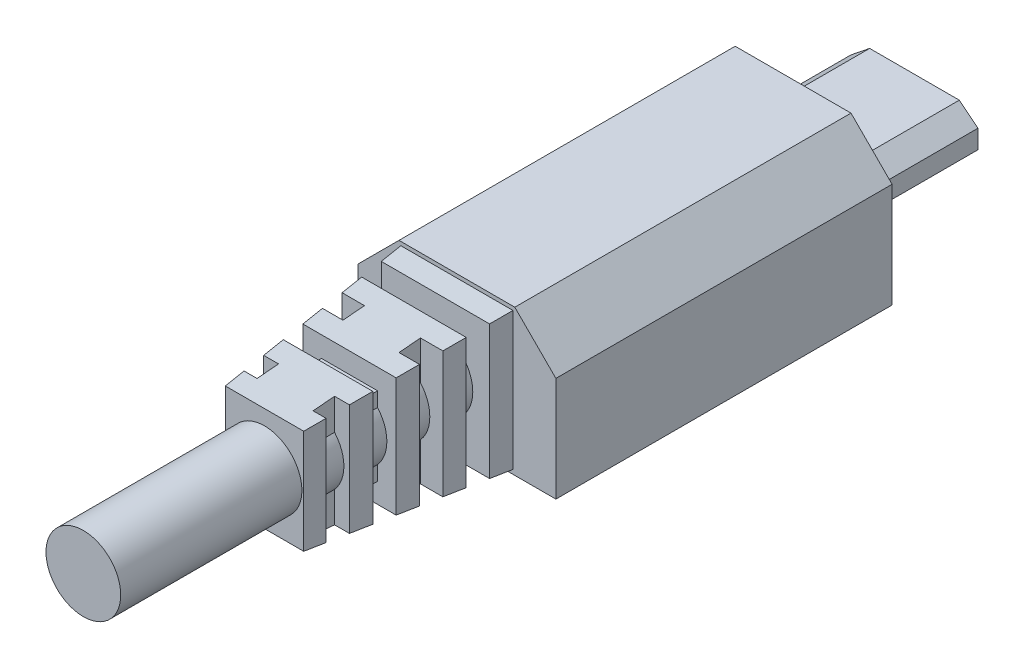
SolidWorks part; units mm, degrees
ref_plane "Front Plane" through (0, 0, 0) normal (0, 0, 1) x (1, 0, 0)
ref_plane "Top Plane" through (0, 0, 0) normal (0, 1, 0) x (1, 0, 0)
ref_plane "Right Plane" through (0, 0, 0) normal (1, 0, 0) x (0, 0, -1)
sketch "Sketch1" plane through (0, 0, 0) normal (0, 0, 1) x (1, 0, 0)
  line L0 (0, 1) -> (1, 1.8)
  line L1 (0, 0) -> (6.8, 0)
  line L2 (0, 0) -> (0, 1.8)
  line L3 (0, 1.8) -> (6.8, 1.8)
  line L4 (6.8, 0) -> (6.8, 1.8)
  line L5 (3.4, 1.8) -> (3.4, 0) construction
  line L6 (6.8, 1) -> (5.8, 1.8)
  line L8 (1.55, 0.2) -> (5.25, 0.2)
  line L9 (1.55, 0.2) -> (1.55, 0.85)
  line L10 (1.55, 0.85) -> (5.25, 0.85)
  line L11 (5.25, 0.2) -> (5.25, 0.85)
  point P15 (3.4, 0.85)
  dimension "D1" = 1.8
  dimension "D2" = 6.8
  dimension "D3" = 1
  dimension "D4" = 1
  dimension "D5" = 0.2
  dimension "D6" = 3.7
  dimension "D7" = 0.65
extrude "Boss-Extrude1" add sketch "Sketch1" along normal blind 6.5 contours L5 L3 L0 L2 L1 L8 L9 L10 | L3 L5 L10 L11 L8 L1 L4 L6 region at (1.6147, 0.9437, 0) region at (5.1853, 0.9437, 0)
sketch "Sketch2" plane through (0, 0, 6.5) normal (0, 0, 1) x (1, 0, 0)
  line L0 (0, 0.7631) -> (-1.9, 0.7631) construction
  line L1 (-1.9, 4.8) -> (8.7, 4.8)
  line L2 (-1.9, 4.8) -> (-1.9, -3)
  line L3 (-1.9, -3) -> (8.7, -3)
  line L4 (8.7, 4.8) -> (8.7, -3)
  line L5 (-1.9, 2.6) -> (0.3, 4.8)
  line L6 (8.7, 2.6) -> (6.5, 4.8)
  line L7 (3.4, 4.8) -> (3.4, 1.8) construction
  line L8 (1, 1.8) -> (5.8, 1.8) construction
  line L9 (3.4, 0) -> (3.4, -3) construction
  line L10 (0, 0) -> (6.8, 0) construction
  line L13 (0, 0) -> (0, 1) construction
  line L14 (6.8, 0.7631) -> (8.7, 0.7631) construction
  line L15 (6.8, 0) -> (6.8, 1) construction
  line M1 (1.55, 0.85) -> (5.25, 0.85)
  line M2 (5.25, 0.85) -> (5.25, 0.2)
  line M3 (5.25, 0.2) -> (1.55, 0.2)
  line M4 (1.55, 0.2) -> (1.55, 0.85)
  line M5 (6.8, 1) -> (5.8, 1.8)
  line M6 (5.8, 1.8) -> (1, 1.8)
  line M7 (1, 1.8) -> (0, 1)
  line M8 (0, 1) -> (0, 0)
  line M9 (0, 0) -> (6.8, 0)
  line M10 (6.8, 0) -> (6.8, 1)
  dimension "D1" = 10.6
  dimension "D2" = 7.8
  dimension "D3" = 2.2
  dimension "D4" = 2.2
extrude "Boss-Extrude2" add sketch "Sketch2" along normal blind 18 contours L4 L6 L1 L5 L2 L3 M5 M10 M9 M8 M7 M6 | M10 M5 M6 M7 M8 M9 M4 M1 M2 M3 | M1 M4 M3 M2 region at (3.4, 4.6684, 6.5) region at (3.4, 0.525, 6.5) region at (3.4, 0.9437, 6.5)
sketch "Sketch5" plane through (0, 0, 24.5) normal (0, 0, 1) x (1, 0, 0)
  line L0 (0.3, 4.8) -> (6.5, 4.8) construction
  line L1 (6.4, 4.6) -> (0.4, 4.6)
  line L2 (6.4, 4.6) -> (6.4, -2.772)
  line L3 (6.4, -2.772) -> (0.4, -2.772)
  line L4 (0.4, 4.6) -> (0.4, -2.772)
  line L6 (3.4, 4.8) -> (3.4, 4.6) construction
  dimension "D1" = 0.2
  dimension "D2" = 6
extrude "Boss-Extrude4" add sketch "Sketch5" along normal blind 10.3 draft 5
sketch "Sketch7" plane through (0, 4.8, 0) normal (0, 1, 0) x (1, 0, 0)
  line L0 (3.4, -24.5) -> (3.4, -36.1996) construction
  line L1 (0.3, -24.5) -> (1.9, -24.5)
  line L2 (0.3, -24.5) -> (0.3, -25.65)
  line L3 (0.3, -25.65) -> (1.9, -25.65)
  line L4 (1.9, -24.5) -> (1.9, -25.65)
  line L5 (1.9, -25.65) -> (-0.2696, -25.65)
  line L6 (1.9, -25.65) -> (1.9, -26.8)
  line L7 (1.9, -26.8) -> (-0.2696, -26.8)
  line L8 (-0.2696, -25.65) -> (-0.2696, -26.8)
  line L9 (1.9, -26.8) -> (-0.2696, -26.8)
  line L10 (1.9, -26.8) -> (1.9, -27.95)
  line L11 (1.9, -27.95) -> (-0.2696, -27.95)
  line L12 (-0.2696, -26.8) -> (-0.2696, -27.95)
  line L13 (1.9, -27.95) -> (-0.2696, -27.95)
  line L14 (1.9, -27.95) -> (1.9, -29.1)
  line L15 (1.9, -29.1) -> (-0.2696, -29.1)
  line L16 (-0.2696, -27.95) -> (-0.2696, -29.1)
  line L17 (1.9, -29.1) -> (-0.2696, -29.1)
  line L18 (1.9, -29.1) -> (1.9, -30.25)
  line L19 (1.9, -30.25) -> (-0.2696, -30.25)
  line L20 (-0.2696, -29.1) -> (-0.2696, -30.25)
  line L21 (1.9, -30.25) -> (-0.2696, -30.25)
  line L22 (1.9, -30.25) -> (1.9, -31.4)
  line L23 (1.9, -31.4) -> (-0.2696, -31.4)
  line L24 (-0.2696, -30.25) -> (-0.2696, -31.4)
  line L25 (1.9, -31.4) -> (-0.2696, -31.4)
  line L26 (1.9, -31.4) -> (1.9, -32.55)
  line L27 (1.9, -32.55) -> (-0.2696, -32.55)
  line L28 (-0.2696, -31.4) -> (-0.2696, -32.55)
  line L29 (1.9, -32.55) -> (-0.2696, -32.55)
  line L30 (1.9, -32.55) -> (1.9, -33.7)
  line L31 (1.9, -33.7) -> (-0.2696, -33.7)
  line L32 (-0.2696, -32.55) -> (-0.2696, -33.7)
  line L33 (1.9, -33.7) -> (-0.2696, -33.7)
  line L34 (1.9, -33.7) -> (1.9, -34.85)
  line L35 (1.9, -34.85) -> (-0.2696, -34.85)
  line L36 (-0.2696, -33.7) -> (-0.2696, -34.85)
  line L37 (6.4, -24.5) -> (0.4, -24.5) construction
  line L38 (7.0696, -33.7) -> (7.0696, -34.85)
  line L39 (4.9, -34.85) -> (7.0696, -34.85)
  line L40 (4.9, -33.7) -> (4.9, -34.85)
  line L41 (4.9, -33.7) -> (7.0696, -33.7)
  line L42 (7.0696, -32.55) -> (7.0696, -33.7)
  line L43 (4.9, -33.7) -> (7.0696, -33.7)
  line L44 (4.9, -32.55) -> (4.9, -33.7)
  line L45 (4.9, -32.55) -> (7.0696, -32.55)
  line L46 (7.0696, -31.4) -> (7.0696, -32.55)
  line L47 (4.9, -32.55) -> (7.0696, -32.55)
  line L48 (4.9, -31.4) -> (4.9, -32.55)
  line L49 (4.9, -31.4) -> (7.0696, -31.4)
  line L50 (7.0696, -30.25) -> (7.0696, -31.4)
  line L51 (4.9, -31.4) -> (7.0696, -31.4)
  line L52 (4.9, -30.25) -> (4.9, -31.4)
  line L53 (4.9, -30.25) -> (7.0696, -30.25)
  line L54 (7.0696, -29.1) -> (7.0696, -30.25)
  line L55 (4.9, -30.25) -> (7.0696, -30.25)
  line L56 (4.9, -29.1) -> (4.9, -30.25)
  line L57 (4.9, -29.1) -> (7.0696, -29.1)
  line L58 (7.0696, -27.95) -> (7.0696, -29.1)
  line L59 (4.9, -29.1) -> (7.0696, -29.1)
  line L60 (4.9, -27.95) -> (4.9, -29.1)
  line L61 (4.9, -27.95) -> (7.0696, -27.95)
  line L62 (7.0696, -26.8) -> (7.0696, -27.95)
  line L63 (4.9, -27.95) -> (7.0696, -27.95)
  line L64 (4.9, -26.8) -> (4.9, -27.95)
  line L65 (4.9, -26.8) -> (7.0696, -26.8)
  line L66 (7.0696, -25.65) -> (7.0696, -26.8)
  line L67 (4.9, -26.8) -> (7.0696, -26.8)
  line L68 (4.9, -25.65) -> (4.9, -26.8)
  line L69 (4.9, -25.65) -> (7.0696, -25.65)
  line L70 (4.9, -24.5) -> (4.9, -25.65)
  line L71 (6.5, -25.65) -> (4.9, -25.65)
  line L72 (6.5, -24.5) -> (6.5, -25.65)
  line L73 (6.5, -24.5) -> (4.9, -24.5)
  dimension "D1" = 1.15
  dimension "D2" = 1.6
extrude "Cut-Extrude1" cut sketch "Sketch7" against normal blind 10.3 contours L5 L8 L7 L6 L3 | L11 L16 L15 L14 | L19 L24 L23 L22 | L27 L32 L31 L30 | L69 L68 L65 L66 | L61 L60 L57 L58 | L53 L52 L49 L50 | L45 L44 L41 L42 region at (0.8152, 4.8, 26.225) region at (0.8152, 4.8, 28.525) region at (0.8152, 4.8, 30.825) region at (0.8152, 4.8, 33.125) region at (5.9848, 4.8, 33.125) region at (5.9848, 4.8, 30.825) region at (5.9848, 4.8, 28.525) region at (5.9848, 4.8, 26.225)
ref_plane "Plane1" through (6.4, -2.772, 24.5) normal (0, 1, 0) x (1, 0, 0)
sketch "Sketch9" plane through (8.7, 0, 0) normal (1, 0, 0) x (0, 0, -1)
  line L0 (-36.8785, 0.9) -> (-25.1788, 0.9) construction
  line L1 (-34.85, -2.8) -> (-34.85, -1.2)
  line L2 (-34.85, -2.8) -> (-33.7, -2.8)
  line L3 (-33.7, -2.8) -> (-33.7, -1.2)
  line L4 (-34.85, -1.2) -> (-33.7, -1.2)
  line L5 (-33.7, -1.2) -> (-33.7, -2.8)
  line L6 (-33.7, -1.2) -> (-32.55, -1.2)
  line L7 (-32.55, -1.2) -> (-32.55, -2.8)
  line L8 (-33.7, -2.8) -> (-32.55, -2.8)
  line L9 (-32.55, -1.2) -> (-32.55, -2.8)
  line L10 (-32.55, -1.2) -> (-31.4, -1.2)
  line L11 (-31.4, -1.2) -> (-31.4, -2.8)
  line L12 (-32.55, -2.8) -> (-31.4, -2.8)
  line L13 (-31.4, -1.2) -> (-31.4, -2.8)
  line L14 (-31.4, -1.2) -> (-30.25, -1.2)
  line L15 (-30.25, -1.2) -> (-30.25, -2.8)
  line L16 (-31.4, -2.8) -> (-30.25, -2.8)
  line L17 (-30.25, -1.2) -> (-30.25, -2.8)
  line L18 (-30.25, -1.2) -> (-29.1, -1.2)
  line L19 (-29.1, -1.2) -> (-29.1, -2.8)
  line L20 (-30.25, -2.8) -> (-29.1, -2.8)
  line L21 (-29.1, -1.2) -> (-29.1, -2.8)
  line L22 (-29.1, -1.2) -> (-27.95, -1.2)
  line L23 (-27.95, -1.2) -> (-27.95, -2.8)
  line L24 (-29.1, -2.8) -> (-27.95, -2.8)
  line L25 (-27.95, -1.2) -> (-27.95, -2.8)
  line L26 (-27.95, -1.2) -> (-26.8, -1.2)
  line L27 (-26.8, -1.2) -> (-26.8, -2.8)
  line L28 (-27.95, -2.8) -> (-26.8, -2.8)
  line L29 (-26.8, -1.2) -> (-26.8, -2.8)
  line L30 (-26.8, -1.2) -> (-25.65, -1.2)
  line L31 (-25.65, -1.2) -> (-25.65, -2.8)
  line L32 (-26.8, -2.8) -> (-25.65, -2.8)
  line L33 (-25.65, -1.2) -> (-25.65, -2.8)
  line L34 (-25.65, -1.2) -> (-24.5, -1.2)
  line L35 (-24.5, -1.2) -> (-24.5, -2.8)
  line L36 (-25.65, -2.8) -> (-24.5, -2.8)
  line L37 (-25.65, 4.6) -> (-24.5, 4.6)
  line L38 (-24.5, 3) -> (-24.5, 4.6)
  line L39 (-25.65, 3) -> (-24.5, 3)
  line L40 (-25.65, 3) -> (-25.65, 4.6)
  line L41 (-26.8, 4.6) -> (-25.65, 4.6)
  line L42 (-25.65, 3) -> (-25.65, 4.6)
  line L43 (-26.8, 3) -> (-25.65, 3)
  line L44 (-26.8, 3) -> (-26.8, 4.6)
  line L45 (-27.95, 4.6) -> (-26.8, 4.6)
  line L46 (-26.8, 3) -> (-26.8, 4.6)
  line L47 (-27.95, 3) -> (-26.8, 3)
  line L48 (-27.95, 3) -> (-27.95, 4.6)
  line L49 (-29.1, 4.6) -> (-27.95, 4.6)
  line L50 (-27.95, 3) -> (-27.95, 4.6)
  line L51 (-29.1, 3) -> (-27.95, 3)
  line L52 (-29.1, 3) -> (-29.1, 4.6)
  line L53 (-30.25, 4.6) -> (-29.1, 4.6)
  line L54 (-29.1, 3) -> (-29.1, 4.6)
  line L55 (-30.25, 3) -> (-29.1, 3)
  line L56 (-30.25, 3) -> (-30.25, 4.6)
  line L57 (-31.4, 4.6) -> (-30.25, 4.6)
  line L58 (-30.25, 3) -> (-30.25, 4.6)
  line L59 (-31.4, 3) -> (-30.25, 3)
  line L60 (-31.4, 3) -> (-31.4, 4.6)
  line L61 (-32.55, 4.6) -> (-31.4, 4.6)
  line L62 (-31.4, 3) -> (-31.4, 4.6)
  line L63 (-32.55, 3) -> (-31.4, 3)
  line L64 (-32.55, 3) -> (-32.55, 4.6)
  line L65 (-33.7, 4.6) -> (-32.55, 4.6)
  line L66 (-32.55, 3) -> (-32.55, 4.6)
  line L67 (-33.7, 3) -> (-32.55, 3)
  line L68 (-33.7, 3) -> (-33.7, 4.6)
  line L69 (-34.85, 3) -> (-33.7, 3)
  line L70 (-33.7, 4.6) -> (-33.7, 3)
  line L71 (-34.85, 4.6) -> (-33.7, 4.6)
  line L72 (-34.85, 4.6) -> (-34.85, 3)
  dimension "D1" = 1.15
  dimension "D2" = 1.6
  dimension "D3" = 2.1
extrude "Cut-Extrude2" cut sketch "Sketch9" against normal blind 10.3 contours L44 L43 L40 L41 | L60 L59 L56 L57 | L27 L32 L31 L30 | L11 L16 L15 L14 region at (8.7, -2, 30.825) region at (8.7, -2, 26.225) region at (8.7, 3.8, 26.225) region at (8.7, 3.8, 30.825)
sketch "Sketch3" plane through (0, 0, 24.5) normal (0, 0, 1) x (1, 0, 0)
  line L0 (3.4, 4.8) -> (3.4, 0.9) construction
  line L1 (0.3, 4.8) -> (6.5, 4.8) construction
  line L2 (3.4, 0.9) -> (-1.9, 0.9) construction
  line L3 (-1.9, 2.6) -> (-1.9, -3) construction
  line L4 (3.4, 0.9) -> (3.4, -3) construction
  line L5 (-1.9, -3) -> (8.7, -3) construction
  line L6 (3.4, 0.9) -> (8.7, 0.9) construction
  line L7 (8.7, 2.6) -> (8.7, -3) construction
  line L8 (8.7, 4.8) -> (8.7, -3) construction
  circle A0 centre (3.4, 0.9) radius 2
extrude "Boss-Extrude3" add sketch "Sketch3" along normal blind 20
ref_plane "Plane2" through (0, 0.9, 0) normal (0, -1, 0) x (-1, 0, 0)
ref_plane "Plane3" through (3.4, 0, 0) normal (1, 0, 0) x (0, 0, -1)
